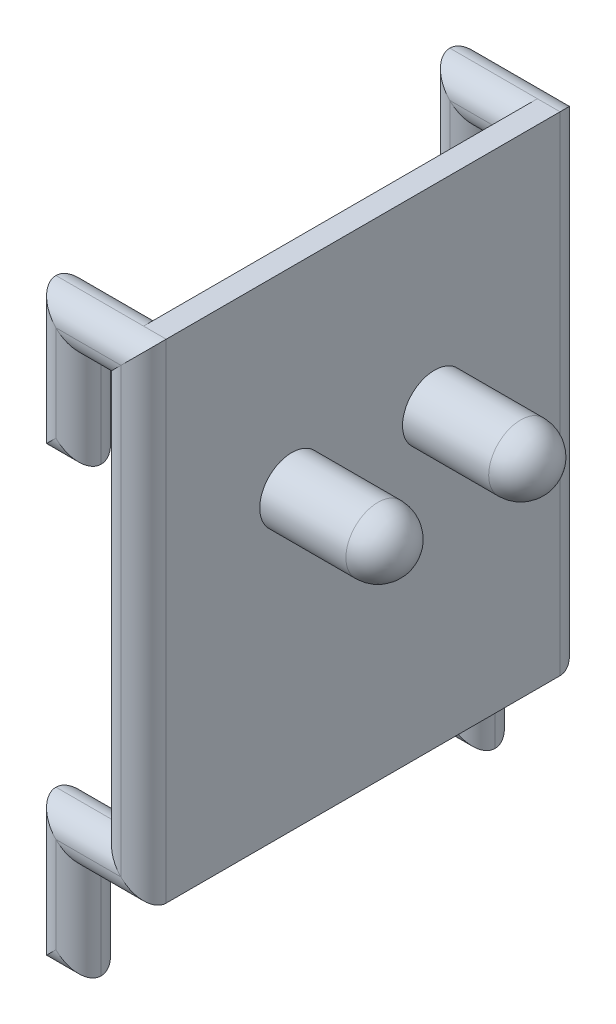
SolidWorks part; units mm, degrees
ref_plane "Plan de face" through (0, 0, 0) normal (0, 0, 1) x (1, 0, 0)
ref_plane "Plan de dessus" through (0, 0, 0) normal (0, 1, 0) x (1, 0, 0)
ref_plane "Plan de droite" through (0, 0, 0) normal (1, 0, 0) x (0, 0, -1)
sketch "Esquisse1" plane through (0, 0, 0) normal (0, 0, 1) x (1, 0, 0)
  line L0 (0, 0) -> (-6.6, 0)
  line L1 (-6.6, 0) -> (-6.6, -12)
  line L2 (0, 0) -> (0, -45)
  line L3 (0, -45) -> (-6.6, -45)
  line L4 (-6.6, -45) -> (-6.6, -57)
  dimension "D1" = 45
  dimension "D2" = 12
  dimension "D3" = 6.6
extrude "Extru.-Mince1" add sketch "Esquisse1" along normal mid plane 4.6 thin
fillet "Congé1" radius 2.3 24 edges at (-6.6, -57, -2.3) (-4.3, -52.15, -2.3) (-1, -47.3, -2.3) (2.3, -22.5, -2.3) (-3.3, 2.3, -2.3) (-8.9, -4.85, -2.3) (-6.6, -12, -2.3) (-4.3, -7.15, -2.3) (-3.3, -2.3, -2.3) (-2.3, -22.5, -2.3) (-5.6, -42.7, -2.3) (-8.9, -49.85, -2.3) (-5.6, -42.7, 2.3) (-2.3, -22.5, 2.3) (-3.3, -2.3, 2.3) (-4.3, -7.15, 2.3) (-6.6, -12, 2.3) (-8.9, -4.85, 2.3) (-3.3, 2.3, 2.3) (2.3, -22.5, 2.3) (-1, -47.3, 2.3) (-4.3, -52.15, 2.3) (-6.6, -57, 2.3) (-8.9, -49.85, 2.3)
sketch "Esquisse2" plane through (0, 0, 0) normal (1, 0, 0) x (0, 0, -1)
  line L1 (0, -47.3) -> (-40, -47.3)
  line L2 (0, -47.3) -> (0, 2.3)
  line L3 (0, 2.3) -> (-40, 2.3)
  line L4 (-40, -47.3) -> (-40, 2.3)
  point P5 (0, 2.3)
  dimension "D1" = 40
extrude "Boss.-Extru.1" add sketch "Esquisse2" along normal up to vertex (2.3 mm away) up to point (2.3, 2.3, 0)
pattern_linear "Répétition linéaire1" count 2 spacing 40 along (0, 0, 1) of "Extru.-Mince1"
fillet "Congé2" radius 2.3 23 edges at (-5.6, -42.7, 42.3) (-2.3, -22.5, 42.3) (-3.3, -2.3, 42.3) (-4.3, -7.15, 42.3) (-6.6, -12, 42.3) (-8.9, -4.85, 42.3) (-3.3, 2.3, 42.3) (2.3, -22.5, 42.3) (-1, -47.3, 42.3) (-4.3, -52.15, 42.3) (-6.6, -57, 42.3) (-8.9, -49.85, 42.3) (-2.15, -47.3, 37.7) (-4.3, -52.15, 37.7) (-6.6, -57, 37.7) (-8.9, -49.85, 37.7) (-5.6, -42.7, 37.7) (-2.3, -22.5, 37.7) (-3.3, -2.3, 37.7) (-4.3, -7.15, 37.7) (-6.6, -12, 37.7) (-8.9, -4.85, 37.7) (-4.45, 2.3, 37.7)
sketch "Esquisse3" plane through (2.3, 0, 0) normal (1, 0, 0) x (0, 0, -1)
  line L0 (-20, -47.3) -> (-20, -17.3) construction
  line L1 (-40, -47.3) -> (0, -47.3) construction
  line L2 (-27.25, -17.3) -> (-12.75, -17.3) construction
  circle A0 centre (-27.25, -17.3) radius 3.25
  circle A1 centre (-12.75, -17.3) radius 3.25
  dimension "D3" = 6.5
  dimension "D1" = 30
  dimension "D2" = 14.5
extrude "Boss.-Extru.2" add sketch "Esquisse3" along normal blind 12
fillet "Congé3" radius 3.25 2 edges at (14.3, -17.3, 9.5) (14.3, -17.3, 24)
